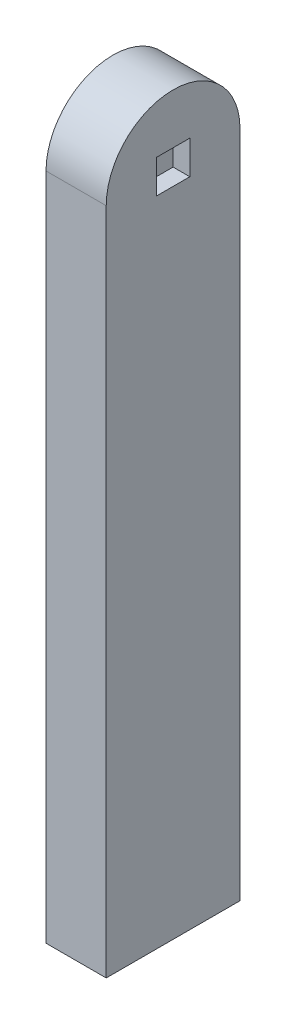
SolidWorks part; units mm, degrees
ref_plane "Front Plane" through (0, 0, 0) normal (0, 0, 1) x (1, 0, 0)
ref_plane "Top Plane" through (0, 0, 0) normal (0, 1, 0) x (1, 0, 0)
ref_plane "Right Plane" through (0, 0, 0) normal (1, 0, 0) x (0, 0, -1)
sketch "Sketch2" plane through (0, 0, 0) normal (1, 0, 0) x (0, 0, -1)
  line L0 (-20, 0) -> (20, 0) construction
  line L1 (-20, 0) -> (-20, -200)
  line L2 (20, 0) -> (20, -200)
  line L3 (0, 0) -> (0, 20) construction
  line L11 (-20, -200) -> (20, -200) construction
  line L12 (0, 0) -> (0, -150) construction
  line L13 (15, 0) -> (15, -195)
  line L14 (-15, 0) -> (-15, -195)
  line L15 (-20, -200) -> (20, -200)
  line L16 (-15, -195) -> (15, -195)
  line L17 (-15, 48) -> (-15, -203.5556) construction
  line L18 (15, 48) -> (15, -203.5556) construction
  line L19 (0, -150) -> (0, -187) construction
  line L20 (-20, -187) -> (20, -187) construction
  line L21 (-20, 48) -> (-20, -200) construction
  line L22 (-5, -5) -> (5, -5)
  line L23 (-5, -5) -> (-5, 5)
  line L24 (-5, 5) -> (5, 5)
  line L25 (5, -5) -> (5, 5)
  line L26 (-5, -5) -> (5, 5) construction
  line L27 (-5, 5) -> (5, -5) construction
  line L29 (20, 48) -> (20, -200) construction
  arc A7 (-20, -200) -> (20, -200) centre (0, -252) ccw construction
  arc A8 (-15, -203.5556) -> (15, -203.5556) centre (0, -252) ccw construction
  arc A9 (20, 0) -> (-20, 0) centre (0, 0) ccw
  arc A10 (15, 0) -> (-15, 0) centre (0, 0) ccw
  arc A11 (-20, 48) -> (20, 48) centre (0, 48) cw construction
  arc A12 (-15, 48) -> (15, 48) centre (0, 48) cw construction
  dimension "D2" = 40
  dimension "D6" = 150
  dimension "D8" = 5
  dimension "D10" = 8
  dimension "D11" = 10
  dimension "D3" = 200
  dimension "D9" = 5
sketch "Sketch3" plane through (0, 0, 0) normal (0, 0, 1) x (1, 0, 0)
  line L0 (-145.1347, 0) -> (145.1347, 0) construction
  line L1 (0, -164.4063) -> (0, 164.4063) construction
  line L2 (0, 0) -> (0, -200) construction
  point P3 (-4, 0)
  point P7 (-9, 0)
  point P12 (0, 0)
  dimension "D1" = 18
  dimension "D2" = 5
extrude "Boss-Extrude1" add sketch "Sketch2" along normal up to vertex (-4 mm away) from vertex contours L1 L15 L2 L14 L13 | L14 L13 region at (0, 17.7639, 0) region at (0, -93.0829, 0) up to point (-4, 0, 0) starting at point (-9, 0, 0)
extrude "Boss-Extrude2" add sketch "Sketch2<6>" along normal up to surface from vertex up to plane "Right Plane" starting at point (-4, 0, 0)
sketch "Sketch2<6>" plane through (0, 0, 0) normal (1, 0, 0) x (0, 0, -1) same geometry as "Sketch2"
mirror "Mirror1" about plane through (0, 0, 0) normal (1, 0, 0) of bodies 103
equation "\"D8@Sketch2\"=\"D9@Sketch2\""
